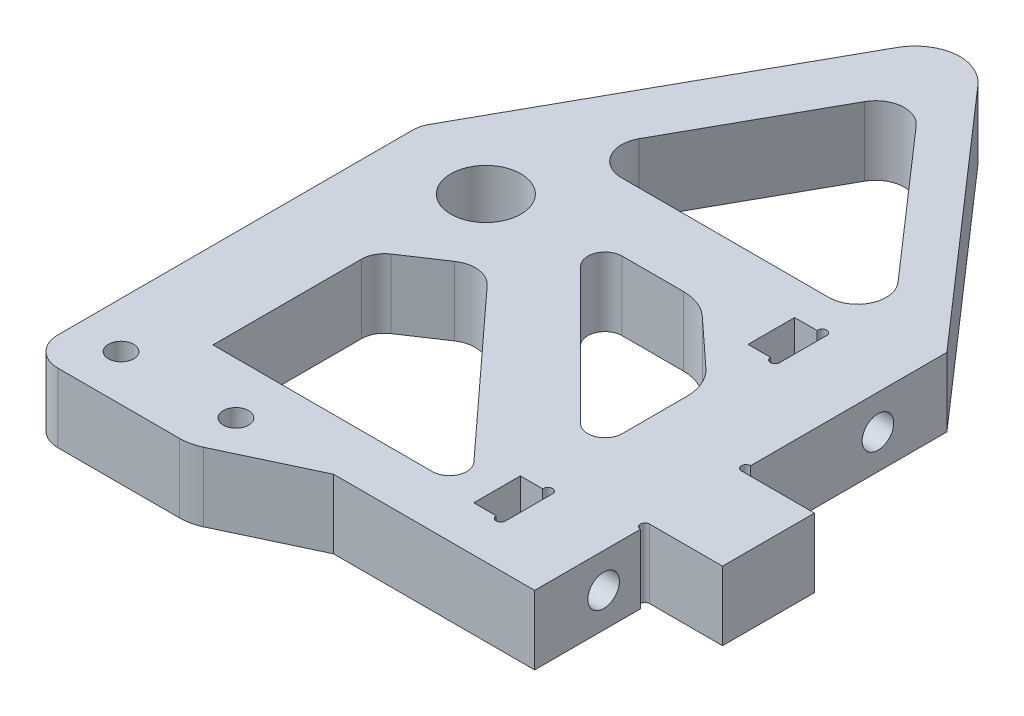
SolidWorks part; units mm, degrees
material "6061 Alloy"
ref_plane "Front Plane" through (0, 0, 0) normal (0, 0, 1) x (1, 0, 0)
ref_plane "Top Plane" through (0, 0, 0) normal (0, 1, 0) x (1, 0, 0)
ref_plane "Right Plane" through (0, 0, 0) normal (1, 0, 0) x (0, 0, -1)
sketch "Sketch1" plane through (0, 0, 0) normal (0, 1, 0) x (1, 0, 0)
  line L1 (-80, 0) -> (-80, 60)
  line L8 (-52, -8) -> (-80, -8)
  line L9 (-80, -8) -> (-80, 0)
  line L10 (-80, 60) -> (-48, 117.5)
  line L11 (-48, 117.5) -> (-40, 117.5)
  line L12 (-40, 117.5) -> (0, 71.75)
  line L14 (0, 36) -> (12.7, 36)
  line L15 (12.7, 36) -> (12.7, 20)
  line L16 (12.7, 20) -> (0, 20)
  line L18 (0, 18.4) -> (0, 0)
  line L19 (0, 71.75) -> (0, 37.6)
  line L20 (-52, -8) -> (-35, 0)
  line L21 (-35, 0) -> (0, 0)
  circle A0 centre (-64, 55.5) radius 6.1
  circle A3 centre (-72, 0) radius 2.2
  circle A4 centre (-52, 0) radius 2.2
  arc A5 (0, 20) -> (0, 18.4) centre (0, 19.2) ccw
  arc A6 (0, 36) -> (0, 37.6) centre (0, 36.8) cw
  point P23 (12.7, 28)
  dimension "D8" = 12.2
  dimension "D19" = 0.8
  dimension "D20" = 0.8
  dimension "D12" = 4.4
  dimension "D16" = 4.4
  dimension "D1" = 80
  dimension "D2" = 71.75
  dimension "D3" = 60
  dimension "D9" = 16
  dimension "D14" = 8
  dimension "D15" = 20
  dimension "D10" = 8
  dimension "D13" = 8
  dimension "D17" = 55.5
  dimension "D4" = 57.5
  dimension "D5" = 32
  dimension "D6" = 8
  dimension "D18" = 12.7
  dimension "D7" = 28
  dimension "D11" = 16
  dimension "D21" = 35
extrude "Boss-Extrude1" add sketch "Sketch1" along normal blind 12
fillet "Fillet1" radius 8 2 edges at (-40, 6, -117.5) (-48, 6, -117.5)
sketch "Sketch3" plane through (0, 12, 0) normal (0, 1, 0) x (1, 0, 0)
  line L5 (-7.5496, 69.75) -> (-41.5119, 108.5944)
  line L6 (-41.5119, 108.5944) -> (-63.1296, 69.75)
  line L7 (-63.1296, 69.75) -> (-7.5496, 69.75)
  line L10 (0, 71.75) -> (-37.6094, 114.7657) construction
  line L11 (-50.2871, 113.3903) -> (-80, 60) construction
  line L16 (-80, 60) -> (-80, -8) construction
  line L17 (-65, 37) -> (-65, 9)
  line L18 (-53, 45) -> (-65, 37)
  line L20 (-42.7574, 58) -> (-32.1279, 58)
  line L21 (-26.7016, 55.8784) -> (-18.5738, 48.3758)
  line L22 (-16, 42.4974) -> (-16, 31.2426)
  line L23 (-21.1213, 29.1213) -> (-44.8787, 52.8787)
  line L25 (-53, 45) -> (-20, 9)
  line L26 (-20, 9) -> (-65, 9)
  arc A4 (-21.1213, 29.1213) -> (-16, 31.2426) centre (-19, 31.2426) ccw
  arc A5 (-44.8787, 52.8787) -> (-42.7574, 58) centre (-42.7574, 55) cw
  arc A6 (-16, 42.4974) -> (-18.5738, 48.3758) centre (-24, 42.4974) ccw
  arc A7 (-26.7016, 55.8784) -> (-32.1279, 58) centre (-32.1279, 50) ccw
  point P19 (-16, 24)
  point P21 (-16, 58)
  point P23 (-50, 58)
  point P24 (-50, 58)
  point P27 (-16, 24)
  point P30 (-24, 8)
  point P31 (-16, 46)
  point P34 (-29, 58)
  point P36 (-58, 42)
  dimension "D14" = 15
  dimension "D8" = 3
  dimension "D9" = 8
  dimension "D15" = 45
  dimension "D1" = 7
  dimension "D2" = 10
  dimension "D3" = 10
  dimension "D4" = 7
  dimension "D5" = 2
  dimension "D6" = 22
  dimension "D7" = 13
  dimension "D10" = 64
  dimension "D11" = 32
  dimension "D12" = 34
  dimension "D13" = 34
  dimension "D16" = 36
  dimension "D17" = 28
  dimension "D18" = 12
extrude "Cut-Extrude1" cut sketch "Sketch3" against normal through all
fillet "Fillet2" radius 5 3 edges at (-41.5119, 6, -108.5944) (-7.5496, 6, -69.75) (-63.1296, 6, -69.75)
sketch "Sketch4" plane through (0, 12, 0) normal (0, 1, 0) x (1, 0, 0)
  line L0 (0, 0) -> (0, 18.4) construction
  line L2 (-18.5, 16) -> (-18.5, 7.9)
  line L4 (-13, 16.1) -> (-13, 7.9)
  line L5 (-18.5, 16) -> (-14.5937, 16)
  line L6 (-18.5, 7.9) -> (-14.6, 7.9)
  line L7 (-18.5, 55.65) -> (-14.6, 55.65)
  line L8 (-13, 63.85) -> (-13, 55.65)
  line L9 (-18.5, 63.75) -> (-14.5937, 63.75)
  line L10 (-18.5, 63.75) -> (-18.5, 55.65)
  arc A0 (-13, 16.1) -> (-14.5937, 16) centre (-13.8, 16.1) ccw
  arc A1 (-13, 7.9) -> (-14.6, 7.9) centre (-13.8, 7.9) cw
  arc A2 (-13, 55.65) -> (-14.6, 55.65) centre (-13.8, 55.65) cw
  arc A3 (-13, 63.85) -> (-14.5937, 63.75) centre (-13.8, 63.85) ccw
  point P4 (-13, 12)
  point P12 (-13, 59.75)
  dimension "D5" = 0.8
  dimension "D2" = 13
  dimension "D3" = 8.2
  dimension "D4" = 5.5
  dimension "D7" = 12
  dimension "D1" = 12
  dimension "D6" = 2
extrude "Cut-Extrude2" cut sketch "Sketch4" against normal through all
sketch "Sketch6" plane through (-13, 0, 0) normal (-1, 0, 0) x (0, 0, 1)
  line L0 (-7.9, 0) -> (-7.9, 12) construction
  line L1 (-7.9, 12) -> (-16.1, 12) construction
  line L2 (-55.65, 0) -> (-55.65, 12) construction
  line L3 (-60, 12) -> (8, 12) construction
  circle A0 centre (-12, 6) radius 2.75
  circle A1 centre (-59.75, 6) radius 2.75
  dimension "D2" = 5.5
  dimension "D5" = 5.5
  dimension "D1" = 4.1
  dimension "D4" = 4.1
  dimension "D6" = 6
extrude "Cut-Extrude3" cut sketch "Sketch6" against normal through all
fillet "Fillet4" radius 5 2 edges at (-80, 6, 8) (-80, 6, -60)
fillet "Fillet5" radius 8 1 edges at (-52, 6, 8)
fillet "Fillet6" radius 3 1 edges at (-20, 6, -9)
fillet "Fillet7" radius 5 1 edges at (-53, 6, -45)
fillet "Fillet8" radius 4 1 edges at (-65, 6, -37)
equation "\"DriveMotorLength\"= 90mm"
equation "\"DriveMotorGap\"= 10mm"
equation "\"AluminumThickness\"= 0.5in"
equation "\"ChassisWidth\"= ( \"DriveMotorLength\" + \"AluminumThickness\" ) * 2 + \"DriveMotorGap\""
equation "\"RepeatMagnumHoleWidth\"= 19.05mm"
equation "\"MortiseWidth\"= 16mm"
equation "\"ChassisScrewThruHole\"= 5.5mm"
equation "\"MortiseSlotWidth\"= 16.2mm"
equation "\"Dogbone\"= 0.8mm"
equation "\"D19@Sketch1\"=\"Dogbone\""
equation "\"D20@Sketch1\"=\"Dogbone\""
equation "\"D5@Sketch4\"=\"Dogbone\""
equation "\"D2@Sketch6\"=\"ChassisScrewThruHole\""
equation "\"D5@Sketch6\"=\"ChassisScrewThruHole\""
equation "\"D11@Sketch1\"=\"MortiseWidth\""
